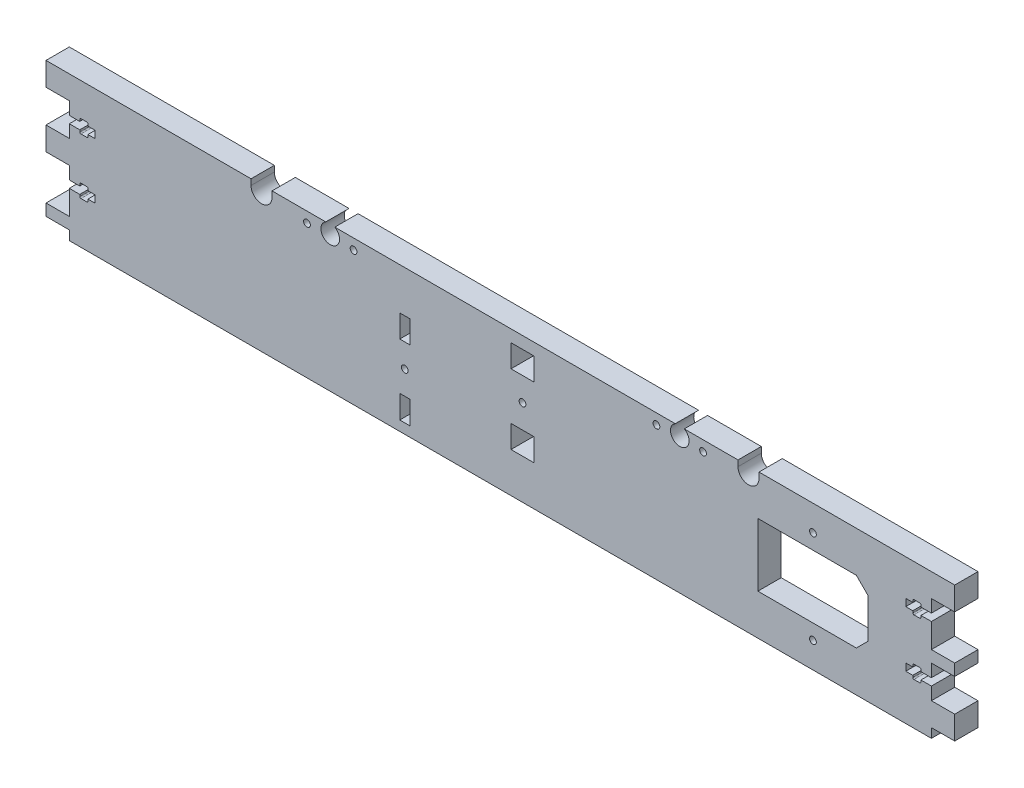
SolidWorks part; units mm, degrees
ref_plane "Front Plane" through (0, 0, 0) normal (0, 0, 1) x (1, 0, 0)
ref_plane "Top Plane" through (0, 0, 0) normal (0, 1, 0) x (1, 0, 0)
ref_plane "Right Plane" through (0, 0, 0) normal (1, 0, 0) x (0, 0, -1)
sketch "Sketch1" plane through (0, 0, 0) normal (0, 0, 1) x (1, 0, 0)
  line L0 (0, 0) -> (-185, 0)
  line L1 (-185, 0) -> (-185, -62) construction
  line L2 (0, -62) -> (-185, -62)
  line L3 (-185, -62) -> (-185, -58)
  line L4 (-185, -58) -> (-195, -58)
  line L5 (-195, -58) -> (-195, -48)
  line L6 (-195, -48) -> (-185, -48)
  line L7 (-185, -48) -> (-185, -34)
  line L8 (-185, -34) -> (-195, -34)
  line L9 (-195, -34) -> (-195, -24)
  line L10 (-195, -24) -> (-185, -24)
  line L11 (0, -62) -> (0, 0)
  line L12 (-185, -24) -> (-185, 0)
  line L13 (-195, -58) -> (-195, -24) construction
  line L14 (-195, -29) -> (-185, -29) construction
  line L15 (-195, -53) -> (-185, -53) construction
  dimension "D1" = 185
  dimension "D2" = 10
  dimension "D3" = 10
  dimension "D4" = 10
  dimension "D5" = 24
  dimension "D6" = 29
  dimension "D7" = 62
extrude "MainBody" add sketch "Sketch1" along normal blind 10
sketch "Sketch3" plane through (0, 0, 10) normal (0, 0, 1) x (1, 0, 0)
  line L0 (-185, -17) -> (-174, -17) construction
  line L1 (-185, 0) -> (-185, -24) construction
  line L2 (-185, -18.55) -> (-180.5, -18.55)
  line L3 (-180.5, -18.55) -> (-180.5, -19.35)
  line L4 (-180, -19.85) -> (-177.5, -19.85)
  line L5 (-177, -19.35) -> (-177, -18.55)
  line L6 (-177, -18.55) -> (-174, -18.55)
  line L7 (-174, -18.55) -> (-174, -15.45)
  line L8 (-180.5, -18.55) -> (-177, -18.55) construction
  line L9 (-195, -24) -> (-195, -34) construction
  line L10 (-180.5, -15.45) -> (-177, -15.45) construction
  line L11 (-177, -15.45) -> (-174, -15.45)
  line L12 (-177, -14.65) -> (-177, -15.45)
  line L13 (-180, -14.15) -> (-177.5, -14.15)
  line L14 (-180.5, -15.45) -> (-180.5, -14.65)
  line L15 (-185, -15.45) -> (-180.5, -15.45)
  line L16 (-185, -18.55) -> (-185, -15.45)
  line L17 (-185, -24) -> (-185, -34) construction
  line L19 (-195, -24) -> (-195, -34) construction
  line L20 (-195, -29) -> (-185, -29) construction
  line L21 (-180.5, -42.55) -> (-177, -42.55) construction
  line L22 (-180.5, -39.45) -> (-177, -39.45) construction
  line L23 (-185, -41) -> (-174, -41) construction
  line L24 (-185, -39.45) -> (-185, -42.55)
  line L25 (-185, -42.55) -> (-180.5, -42.55)
  line L26 (-180.5, -42.55) -> (-180.5, -43.35)
  line L27 (-180, -43.85) -> (-177.5, -43.85)
  line L28 (-177, -43.35) -> (-177, -42.55)
  line L29 (-177, -42.55) -> (-174, -42.55)
  line L30 (-174, -39.45) -> (-174, -42.55)
  line L31 (-177, -39.45) -> (-174, -39.45)
  line L32 (-177, -38.65) -> (-177, -39.45)
  line L33 (-180, -38.15) -> (-177.5, -38.15)
  line L34 (-180.5, -39.45) -> (-180.5, -38.65)
  line L35 (-185, -39.45) -> (-180.5, -39.45)
  line L36 (-180.5, -15.45) -> (-177, -15.45) construction
  arc A0 (-177.5, -19.85) -> (-177, -19.35) centre (-177.5, -19.35) ccw
  arc A1 (-180.5, -19.35) -> (-180, -19.85) centre (-180, -19.35) ccw
  arc A2 (-180.5, -14.65) -> (-180, -14.15) centre (-180, -14.65) cw
  arc A3 (-177.5, -14.15) -> (-177, -14.65) centre (-177.5, -14.65) cw
  arc A4 (-177.5, -43.85) -> (-177, -43.35) centre (-177.5, -43.35) ccw
  arc A5 (-180.5, -43.35) -> (-180, -43.85) centre (-180, -43.35) ccw
  arc A6 (-180.5, -38.65) -> (-180, -38.15) centre (-180, -38.65) cw
  arc A7 (-177.5, -38.15) -> (-177, -38.65) centre (-177.5, -38.65) cw
  point P6 (-195, -29)
  point P15 (-177, -19.85)
  point P18 (-180.5, -19.85)
  point P29 (-180.5, -14.15)
  point P30 (-177, -14.15)
  point P62 (-177, -43.85)
  point P63 (-180.5, -43.85)
  point P64 (-180.5, -38.15)
  point P65 (-177, -38.15)
  dimension "D2" = 8
  dimension "D7" = 0.5
  dimension "D1" = 11
  dimension "D3" = 1.55
  dimension "D4" = 2.85
  dimension "D5" = 12
  dimension "D6" = 3.5
extrude "ScrewCutouts" cut sketch "Sketch3" against normal through all
mirror "Mirror1" about plane through (0, 0, 0) normal (1, 0, 0) of "ScrewCutouts", "MainBody"
sketch "Sketch2" plane through (0, 0, 10) normal (0, 0, 1) x (1, 0, 0)
  line L0 (0, 0) -> (0, -62) construction
  line L1 (-185, -62) -> (185, -62) construction
  line L2 (2, 0) -> (2, -62) construction
  line L3 (185, 0) -> (-185, 0) construction
  line L4 (-63, -4.5) -> (-83, -4.5) construction
  line L5 (-73, -7.5) -> (-73, 0.5) construction
  line L6 (77, -7.5) -> (77, 0.5) construction
  line L7 (67, -4.5) -> (87, -4.5) construction
  circle A0 centre (-73, -3.5) radius 4
  circle A1 centre (-83, -4.5) radius 1.45
  circle A2 centre (-63, -4.5) radius 1.45
  circle A3 centre (67, -4.5) radius 1.45
  circle A4 centre (87, -4.5) radius 1.45
  circle A5 centre (77, -3.5) radius 4
  dimension "D1" = 2.9
  dimension "D2" = 8
  dimension "D4" = 3.5
  dimension "D5" = 75
  dimension "D6" = 2
  dimension "D3" = 10
  dimension "D7" = 1
extrude "RodCutouts" cut sketch "Sketch2" against normal through all
sketch "Sketch4" plane through (0, 0, 10) normal (0, 0, 1) x (1, 0, 0)
  line L0 (77, -3.5) -> (-73, -3.5) construction
  line L1 (2, -3.5) -> (2, -62) construction
  line L2 (-185, -62) -> (185, -62) construction
  line L3 (9.5, -44.85) -> (9.5, -5.15) construction
  line L4 (75.0635, 0) -> (-71.0635, 0) construction
  line L5 (9.5, -10) -> (9.5, -40) construction
  line L6 (4.575, -5.15) -> (14.425, -5.15)
  line L7 (4.575, -5.15) -> (4.575, -14.85)
  line L8 (4.575, -14.85) -> (14.425, -14.85)
  line L9 (14.425, -5.15) -> (14.425, -14.85)
  line L10 (4.575, -5.15) -> (14.425, -14.85) construction
  line L11 (4.575, -14.85) -> (14.425, -5.15) construction
  line L12 (4.575, -35.15) -> (14.425, -35.15)
  line L13 (4.575, -35.15) -> (4.575, -44.85)
  line L14 (4.575, -44.85) -> (14.425, -44.85)
  line L15 (14.425, -35.15) -> (14.425, -44.85)
  line L16 (4.575, -35.15) -> (14.425, -44.85) construction
  line L17 (4.575, -44.85) -> (14.425, -35.15) construction
  circle A0 centre (9.5, -25) radius 1.45
  point P12 (9.5, -10)
  point P17 (9.5, -40)
  dimension "D8" = 2.9
  dimension "D1" = 9.85
  dimension "D2" = 9.7
  dimension "D3" = 9.85
  dimension "D4" = 9.7
  dimension "D5" = 30
  dimension "D6" = 10
  dimension "D7" = 7.5
extrude "Cut-Extrude3" cut sketch "Sketch4" against normal through all
sketch "Sketch5" plane through (0, 0, 10) normal (0, 0, 1) x (1, 0, 0)
  line L0 (-41, 0) -> (-41, -62) construction
  line L1 (-74.9365, 0) -> (-185, 0) construction
  line L2 (-185, -62) -> (185, -62) construction
  line L3 (-43.175, -27.65) -> (-43.175, -47.85) construction
  line L4 (-43.175, -17.95) -> (-38.825, -17.95)
  line L5 (-43.175, -17.95) -> (-43.175, -27.65)
  line L6 (-43.175, -27.65) -> (-38.825, -27.65)
  line L7 (-38.825, -17.95) -> (-38.825, -27.65)
  line L8 (-43.175, -17.95) -> (-38.825, -27.65) construction
  line L9 (-43.175, -27.65) -> (-38.825, -17.95) construction
  line L10 (-43.175, -47.85) -> (-38.825, -47.85)
  line L11 (-43.175, -47.85) -> (-43.175, -57.75)
  line L12 (-43.175, -57.75) -> (-38.825, -57.75)
  line L13 (-38.825, -47.85) -> (-38.825, -57.75)
  line L14 (-43.175, -47.85) -> (-38.825, -57.75) construction
  line L15 (-43.175, -57.75) -> (-38.825, -47.85) construction
  line L16 (-38.825, -47.85) -> (-38.825, -27.65) construction
  line L17 (-43.175, -37.75) -> (-38.825, -37.75) construction
  line L18 (-73, -3.5) -> (77, -3.5) construction
  line L19 (2, -3.5) -> (2, -62) construction
  line L20 (2, -32.75) -> (-195, -32.75) construction
  line L21 (-195, -24) -> (-195, -34) construction
  line L22 (-34.625, 8.9944) -> (-34.625, 5) construction
  line L23 (75.0635, 0) -> (-71.0635, 0) construction
  line L24 (-31.425, 8.9944) -> (-31.425, 5)
  line L25 (-37.825, 8.9944) -> (-37.825, 5)
  circle A0 centre (-41, -37.75) radius 1.45
  arc A1 (-31.425, 8.9944) -> (-37.825, 8.9944) centre (-34.625, 8.9944) ccw
  arc A2 (-37.825, 5) -> (-31.425, 5) centre (-34.625, 5) ccw
  point P6 (-41, -22.8)
  point P11 (-41, -52.8)
  point P34 (-34.625, 6.9972)
  dimension "D4" = 9.7
  dimension "D5" = 30
  dimension "D6" = 2.9
  dimension "D9" = 3.2
  dimension "D1" = 4.35
  dimension "D2" = 0
  dimension "D3" = 9.9
  dimension "D7" = 43
  dimension "D8" = 5
  dimension "D10" = 5
  dimension "D11" = 1
extrude "EndstopHolder" cut sketch "Sketch5" against normal through all
sketch "Sketch6" plane through (0, 0, 10) normal (0, 0, 1) x (1, 0, 0)
  line L0 (-43.175, -47.85) -> (-43.175, -27.65) construction
  line L1 (-42.35, -47.85) -> (-30.825, -47.85) construction
  line L3 (-30.825, -53.85) -> (-30.825, -41.85) construction
  line L4 (-32.825, -53.85) -> (-32.825, -41.85)
  line L5 (-28.825, -53.85) -> (-28.825, -41.85)
  line L6 (-38.825, -47.85) -> (-43.175, -47.85) construction
  line L7 (-38.825, -57.75) -> (-38.825, -47.85) construction
  arc A0 (-32.825, -53.85) -> (-28.825, -53.85) centre (-30.825, -53.85) ccw
  arc A1 (-28.825, -41.85) -> (-32.825, -41.85) centre (-30.825, -41.85) ccw
  point P10 (-30.825, -47.85)
  dimension "D1" = 2
  dimension "D2" = 12
  dimension "D3" = 8
  dimension "D4" = 0
extrude "EndstopWires" [suppressed] cut sketch "Sketch6" against normal through all
sketch "Sketch7" plane through (0, 0, 10) normal (0, 0, 1) x (1, 0, 0)
  line L0 (-73, -3.5) -> (77, -3.5) construction
  line L1 (2, -3.5) -> (2, -62) construction
  line L3 (-102.5, 0) -> (-102.5, -2.5) construction
  line L4 (-74.9365, 0) -> (-185, 0) construction
  line L5 (-98, 0) -> (-98, -2.5)
  line L6 (-107, 0) -> (-107, -2.5)
  line L7 (106.5, 0) -> (106.5, -2.5) construction
  line L8 (102, 0) -> (102, -2.5)
  line L9 (111, 0) -> (111, -2.5)
  line L10 (-185, -62) -> (185, -62) construction
  arc A0 (-98, 0) -> (-107, 0) centre (-102.5, 0) ccw
  arc A1 (-107, -2.5) -> (-98, -2.5) centre (-102.5, -2.5) ccw
  arc A2 (102, 0) -> (111, 0) centre (106.5, 0) cw
  arc A3 (111, -2.5) -> (102, -2.5) centre (106.5, -2.5) cw
  point P12 (-102.5, -1.25)
  point P19 (106.5, -1.25)
  dimension "D3" = 4.5
  dimension "D1" = 2.5
  dimension "D2" = 104.5
extrude "Cut-Extrude4" cut sketch "Sketch7" against normal through all
ref_plane "Plane1" through (0, -31, 0) normal (0, 1, 0) x (1, 0, 0)
sketch "Sketch8" plane through (0, 0, 10) normal (0, 0, 1) x (1, 0, 0)
  line L0 (133.7748, 0) -> (133.7748, -62) construction
  line L1 (185, 0) -> (111, 0) construction
  line L2 (-185, -62) -> (185, -62) construction
  line L3 (132.2469, -17.485) -> (110.5361, -17.485) construction
  line L4 (151.9576, -17.485) -> (112.5361, -17.485) construction
  line L5 (110.5361, -17.485) -> (110.5361, -44.515)
  line L6 (110.5361, -19.485) -> (110.5361, -42.515) construction
  line L7 (112.5361, -44.515) -> (151.9576, -44.515) construction
  line L8 (110.5361, -44.515) -> (152.7861, -44.515)
  line L9 (152.7861, -44.515) -> (157.7861, -39.515)
  line L10 (157.7861, -39.515) -> (157.7861, -22.485)
  line L11 (157.7861, -22.485) -> (152.7861, -17.485)
  line L12 (152.7861, -17.485) -> (110.5361, -17.485)
  line L13 (157.7861, -38.6866) -> (157.7861, -23.3134) construction
  line L14 (157.2003, -21.8992) -> (153.3719, -18.0708) construction
  line L15 (153.3719, -43.9292) -> (157.2003, -40.1008) construction
extrude "Cut-Extrude5" cut sketch "Sketch8" against normal through all
sketch "Sketch9" plane through (0, 0, 0) normal (0, 0, -1) x (-1, 0, 0)
  line L0 (-105.0611, -31) -> (-163.2611, -31) construction
  line L1 (-105.0611, -43.5977) -> (-105.0611, -18.4023) construction
  line L2 (-163.2611, -18.4023) -> (-163.2611, -43.5977) construction
  circle A0 centre (-134.1611, -11) radius 1.45
  circle A1 centre (-134.1611, -11) radius 1.6 construction
  circle A2 centre (-134.1611, -51) radius 1.45
  dimension "D1" = 2.9
extrude "Cut-Extrude6" cut sketch "Sketch9" against normal through all
sketch "Sketch10" plane through (0, 0, 10) normal (0, 0, 1) x (1, 0, 0)
  line L0 (185, 0) -> (185, -15.45) construction
  line L1 (185, 0) -> (195, 0)
  line L2 (185, 0) -> (185, -10)
  line L3 (185, -10) -> (195, -10)
  line L4 (195, 0) -> (195, -10)
  line L5 (195, -24) -> (195, -10) construction
  line L6 (195, -24) -> (195, -34) construction
  line L7 (174, -18.55) -> (174, -15.45) construction
  point P10 (174, -17)
  point P13 (195, -5)
  dimension "D1" = 12
extrude "Boss-Extrude1" add sketch "Sketch10" against normal through all
mirror "Mirror2" about plane through (0, 0, 0) normal (1, 0, 0) of "Boss-Extrude1"
sketch "Sketch11" plane through (0, 0, 10) normal (0, 0, 1) x (1, 0, 0)
  line L0 (195, -24) -> (195, -34) construction
  line L1 (185, -24) -> (195, -24)
  line L2 (185, -24) -> (185, -29)
  line L3 (185, -29) -> (195, -29)
  line L4 (195, -24) -> (195, -29)
  line L5 (-195, -48) -> (-195, -58) construction
  line L6 (-185, -48) -> (-195, -48)
  line L7 (-185, -48) -> (-185, -53)
  line L8 (-185, -53) -> (-195, -53)
  line L9 (-195, -48) -> (-195, -53)
extrude "Cut-Extrude7" cut sketch "Sketch11" against normal through all
equation "\"Y-ROD-SPACING\"=75"
equation "\"D5@Sketch2\"=\"Y-ROD-SPACING\""
equation "\"Y-BED-OFFSET\"=2"
equation "\"D6@Sketch2\"=\"Y-BED-OFFSET\""
equation "\"T-SLOT-NUT-FILLET-RADIUS\"=0.5"
equation "\"D7@Sketch3\"=\"T-SLOT-NUT-FILLET-RADIUS\""
equation "\"T-SLOT-SCREW-SHAFT-RADIUS\"=1.55"
equation "\"D3@Sketch3\"=\"T-SLOT-SCREW-SHAFT-RADIUS\""
equation "\"T-SLOT-SCREW-SHAFT-CUTOUT-LENGTH\"=11"
equation "\"D1@Sketch3\"=\"T-SLOT-SCREW-SHAFT-CUTOUT-LENGTH\""
equation "\"T-SLOT-NUT-DEPTH\"=3.5"
equation "\"D6@Sketch3\"=\"T-SLOT-NUT-DEPTH\""
equation "\"T-SLOT-NUT-WIDTH\"=2.85"
equation "\"D4@Sketch3\"=\"T-SLOT-NUT-WIDTH\""
equation "\"T-SLOT-NUT-END-DISTANCE\"=8"
equation "\"D2@Sketch3\"=\"T-SLOT-NUT-END-DISTANCE\""
equation "\"ACRYLIC-TAB-CUTOUT-SIZE\"=\"ACRYLIC-THICKNESS\"+\"ACRYLIC-TAB-TOLERANCE\"*2"
equation "\"D1@Sketch4\"=\"ACRYLIC-THICKNESS\"-\"KERF\"*2"
equation "\"D2@Sketch4\"=\"ACRYLIC-TAB-WIDTH\"-\"KERF\"*4"
equation "\"D3@Sketch4\"=\"ACRYLIC-THICKNESS\"-\"KERF\"*2"
equation "\"D4@Sketch4\"=\"ACRYLIC-TAB-WIDTH\"-\"KERF\"*4"
equation "\"ACRYLIC-M3-HOLE\"=2.9"
equation "\"D8@Sketch4\"=\"ACRYLIC-M3-HOLE\""
equation "\"Y-BED-ROD-INSET\"=3.5"
equation "\"D1@Sketch2\"=\"ACRYLIC-M3-HOLE\""
equation "\"D4@Sketch2\"=\"Y-BED-ROD-INSET\""
equation "\"SMOOTHROD-CAP-SCREW-DISTANCE\"=20"
equation "\"D3@Sketch2\"=\"SMOOTHROD-CAP-SCREW-DISTANCE\"/2"
equation "\"ACRYLIC-TAB-WIDTH\"=\"ACRYLIC-THICKNESS\""
equation "\"FRAME-WIDTH-INNER\"=370"
equation "\"D2@Sketch1\"=\"ACRYLIC-TAB-WIDTH\""
equation "\"D3@Sketch1\"=\"ACRYLIC-TAB-WIDTH\""
equation "\"D4@Sketch1\"=\"ACRYLIC-TAB-WIDTH\""
equation "\"D1@Sketch1\"=\"FRAME-WIDTH-INNER\"/2"
equation "\"X-ROD-SPACING\"=45"
equation "\"Z-ROD-SPACING\"=17.5"
equation "\"ACRYLIC-THICKNESS\"=10"
equation "\"ACRYLIC-THICKNESS2\"=4.5"
equation "\"NEMA17-HOLE-SPACING\"=31"
equation "\"NEMA17-CENTRAL-CUTOUT\"=22.5"
equation "\"Z-BRACKET-REACH\"=57"
equation "\"TOP-BRACKET-SPACING\"=40"
equation "\"SMOOTHROD-X-LENGTH\"=350"
equation "\"SMOOTHROD-Y-LENGTH\"=350"
equation "\"SMOOTHROD-Z-LENGTH\"=350"
equation "\"SMOOTHROD-TIGHTENING-HEADROOM\"=.25"
equation "\"LEADSCREW-Z-LENGTH\"=300"
equation "\"SCREW-LENGTH-FRAME\"=\"ACRYLIC-THICKNESS\" + 10"
equation "\"SCREW-HEAD-RADIUS\"=6"
equation "\"PRINTED-X-SMOOTHROD-DIAMETER\"=8.8"
equation "\"PRINTED-X-SMOOTHROD-CUTOUT\"=10"
equation "\"PRINTED-X-BASE-HEIGHT\"=10"
equation "\"PRINTED-LM8UU-CUTOUT-SIZE\"=15.5"
equation "\"PRINTED-LM8UU-CUTOUT-LENGTH\"=24.5"
equation "\"PRINTED-X-IDLER-HEIGHT\"=16"
equation "\"PSU-MOUNTING-WIDTH\"=50"
equation "\"PSU-MOUNTING-HEIGHT\"=150"
equation "\"D1@MainBody\"=\"ACRYLIC-THICKNESS\""
equation "\"D1@Sketch5\"=\"ACRYLIC-THICKNESS2\"-\"KERF\"*2"
equation "\"D3@Sketch5\"=\"ACRYLIC-TAB-CUTOUT-SIZE\""
equation "\"D4@Sketch5\"=\"ACRYLIC-TAB-WIDTH\"-\"KERF\"*4"
equation "\"D6@Sketch5\"=\"ACRYLIC-M3-HOLE\""
equation "\"Y-BED-SCREW-SPACING\"=209"
equation "\"Y-BED-SCREW-CUTOUT-SLOT-HEIGHT\"=2.5"
equation "\"Z-ROD-INSET\"=13.5"
equation "\"Y-BELT-TO-ROD-DISTANCE\"=20"
equation "\"SPOOL-HOLDER-ROD-SPACING\"=150"
equation "\"D1@Sketch7\"=\"Y-BED-SCREW-CUTOUT-SLOT-HEIGHT\""
equation "\"D2@Sketch7\"=\"Y-BED-SCREW-SPACING\"/2"
equation "\"ACRYLIC-TAB-TOLERANCE\"=-.05"
equation "\"SCREW-LENGTH-MOTOR\"=\"ACRYLIC-THICKNESS\" + 5"
equation "\"SCREW-LENGTH-EXTRUDER\"=28"
equation "\"ACRYLIC-X-CARRIAGE-WIDTH\"=55"
equation "\"ACRYLIC-X-CARRIAGE-HEIGHT\"=75"
equation "\"ACRYLIC-X-CARRIAGE-LM8UU-CUTOUT-WIDTH\"=24.25"
equation "\"ACRYLIC-X-CARRIAGE-SCREW-SPACING-X\"=15"
equation "\"ACRYLIC-X-CARRIAGE-SCREW-SPACING-Y\"=33"
equation "\"ACRYLIC-X-CARRIAGE-CENTER-TAB-SPACING\"=14"
equation "\"ACRYLIC-X-CARRIAGE-EXTRUDER-OFFSET\"=26"
equation "\"ACRYLIC-X-CARRIAGE-EXTRUDER-ANGLE\"=90"
equation "\"ACRYLIC-X-CARRIAGE-EXTRUDER-SHELF-DEPTH\"=\"ACRYLIC-X-CARRIAGE-EXTRUDER-OFFSET\" + 28"
equation "\"ACRYLIC-X-CARRIAGE-EXTRUDER-BRACE-SPACING\"=23"
equation "\"ACRYLIC-X-CARRIAGE-EXTRUDER-BRACE-TAB-OFFSET\"=20"
equation "\"ACRYLIC-X-CARRIAGE-EXTRUDER-BRACE-HEIGHT\"=35"
equation "\"ACRYLIC-X-CARRIAGE-EXTRUDER-BRACE-SCREW-SPACING\"=22"
equation "\"PRINTED-M3-HOLE\"=3.5"
equation "\"ACRYLIC-X-CARRIAGE-LM8UU-CUTOUT-HEIGHT\"=11.0"
equation "\"ACRYLIC-X-CARRIAGE-DUAL-WIDTH-MULTIPLIER\"=1.65"
equation "\"ACRYLIC-X-CARRIAGE-DUAL-HOTEND-SPACING\"=42"
equation "\"ACRYLIC-X-CARRIAGE-DUAL-WIDTH\"=75"
equation "\"ACRYLIC-X-CARRIAGE-DUAL-HOTEND-SEPARATION\"=36"
equation "\"ACRYLIC-X-CARRIAGE-DUAL-MOUNT-PLATE-DEPTH\"=75"
equation "\"ACRYLIC-X-CARRIAGE-DUAL-MOUNT-BRACE-WIDTH\"=33"
equation "\"ACRYLIC-X-CARRIAGE-DUAL-MOUNT-SCREW-WIDTH\"=40"
equation "\"BLOWER-FAN-WIDTH\"=15"
equation "\"KERF\"=0.075"
equation "\"PRINTED-M3-NUT-AF\"=6.25"
equation "\"ACRYLIC-X-CARRIAGE-DUAL-FAN-OFFSET\"=52"
equation "\"ACRYLIC-X-CARRIAGE-DUAL-FAN-HEIGHT\"=20"
equation "\"D1@Sketch9\"=\"ACRYLIC-M3-HOLE\""
